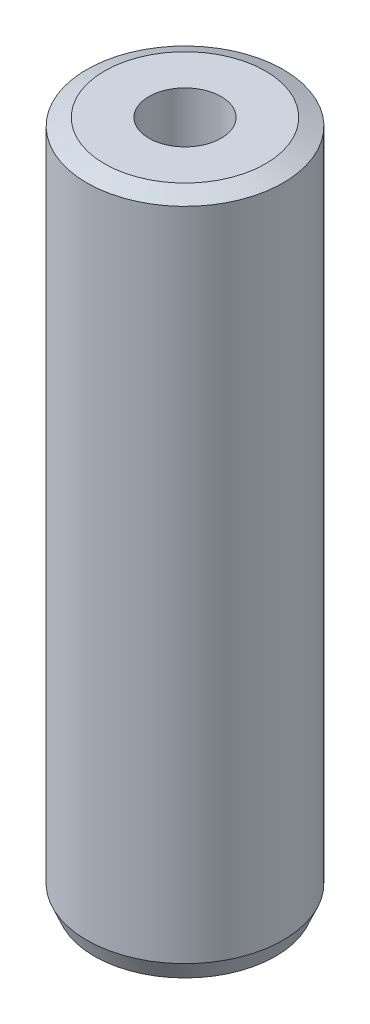
SolidWorks part; units mm, degrees
ref_plane "Front Plane" through (0, 0, 0) normal (0, 0, 1) x (1, 0, 0)
ref_plane "Top Plane" through (0, 0, 0) normal (0, 1, 0) x (1, 0, 0)
ref_plane "Right Plane" through (0, 0, 0) normal (1, 0, 0) x (0, 0, -1)
sketch "Sketch1" plane through (0, 0, 0) normal (0, 1, 0) x (1, 0, 0)
  circle A0 centre (0, 0) radius 60
  dimension "SHAFT_OD" = 120
extrude "Boss-Extrude1" add sketch "Sketch1" along normal blind 416.1127
sketch "Sketch2" plane through (0, 0, 0) normal (0, 1, 0) x (1, 0, 0)
  circle A0 centre (0, 0) radius 22.0843
  dimension "BORE_D" = 44.1685
extrude "Cut-Extrude1" cut sketch "Sketch2" along normal through all
chamfer "Chamfer1" distance 4.6425 angle 66.831 2 edges at (0, 416.1127, 60) (0, 0, 60) first distance on face at (0, 416.1127, 60) first distance on face at (0, 0, 22.0843)
